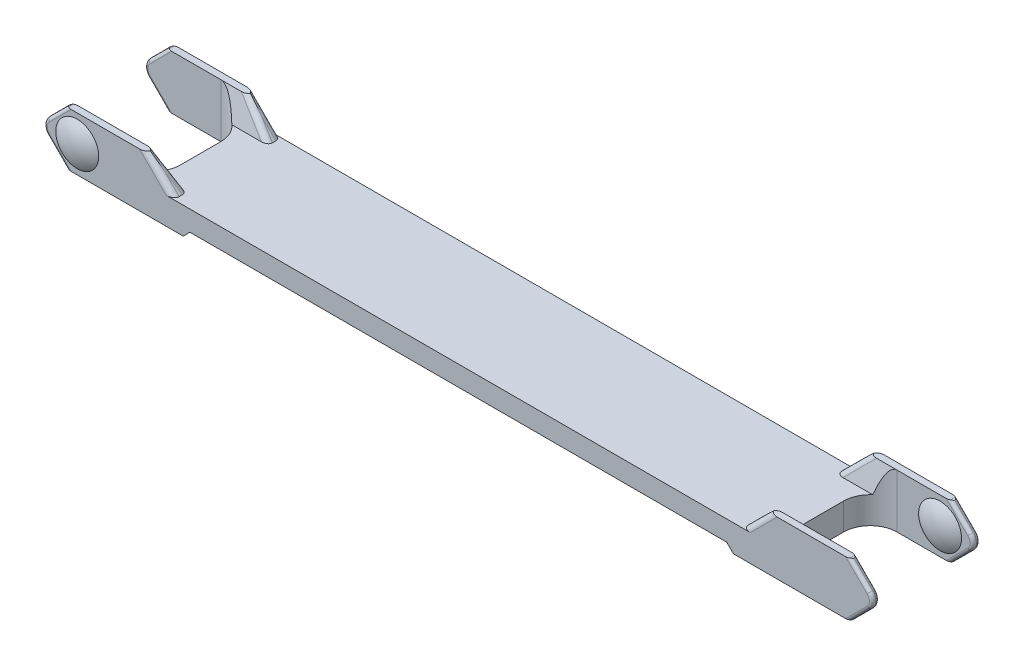
SolidWorks part; units mm, degrees
ref_plane "Front Plane" through (0, 0, 0) normal (0, 0, 1) x (1, 0, 0)
ref_plane "Top Plane" through (0, 0, 0) normal (0, 1, 0) x (1, 0, 0)
ref_plane "Right Plane" through (0, 0, 0) normal (1, 0, 0) x (0, 0, -1)
sketch "Sketch1" plane through (0, 0, 0) normal (0, 1, 0) x (1, 0, 0)
  line L0 (-73.66, 12.7) -> (-73.66, -12.7) construction
  line L1 (-99.06, -12.7) -> (99.06, -12.7)
  line L2 (-99.06, -12.7) -> (-99.06, -11.1125)
  line L3 (-99.06, 12.7) -> (99.06, 12.7)
  line L5 (-99.06, -12.7) -> (99.06, 12.7) construction
  line L6 (-99.06, 12.7) -> (99.06, -12.7) construction
  line L7 (-99.06, 11.1125) -> (-80.01, 11.1125)
  line L8 (-73.66, 4.7625) -> (-73.66, -4.7625)
  line L9 (-80.01, -11.1125) -> (-99.06, -11.1125)
  line L10 (-99.06, 11.1125) -> (-99.06, 12.7)
  line L11 (0, 0) -> (0, 12.7) construction
  line L12 (99.06, 12.7) -> (99.06, 11.1125)
  line L13 (99.06, -12.7) -> (99.06, -11.1125)
  line L14 (80.01, -11.1125) -> (99.06, -11.1125)
  line L15 (73.66, 4.7625) -> (73.66, -4.7625)
  line L16 (99.06, 11.1125) -> (80.01, 11.1125)
  arc A0 (-73.66, -4.7625) -> (-80.01, -11.1125) centre (-80.01, -4.7625) cw
  arc A1 (-80.01, 11.1125) -> (-73.66, 4.7625) centre (-80.01, 4.7625) cw
  arc A2 (73.66, -4.7625) -> (80.01, -11.1125) centre (80.01, -4.7625) ccw
  arc A3 (80.01, 11.1125) -> (73.66, 4.7625) centre (80.01, 4.7625) ccw
  point P0 (0, 0)
  point P14 (-73.66, -11.1125)
  point P17 (-73.66, 11.1125)
  dimension "D6" = 6.35
  dimension "D1" = 198.12
  dimension "D2" = 25.4
  dimension "D3" = 25.4
  dimension "D4" = 1.5875
  dimension "D5" = 1.5875
extrude "Boss-Extrude1" add sketch "Sketch1" along normal blind 12.7
sketch "Sketch3" plane through (-99.06, 0, 0) normal (-1, 0, 0) x (0, 0, 1)
  line L7 (11.1125, 12.7) -> (4.7625, 12.7) construction
  line L8 (-4.7625, 12.7) -> (4.7625, 12.7) construction
  line L9 (-4.7625, 12.7) -> (-11.1125, 12.7) construction
  line L19 (11.1125, 12.7) -> (4.7625, 12.7)
  line L20 (-4.7625, 12.7) -> (4.7625, 12.7)
  line L21 (-4.7625, 12.7) -> (-11.1125, 12.7)
  line L24 (0, 0) -> (0, 12.7) construction
  line L25 (-12.7, 6.35) -> (12.7, 6.35) construction
  line L26 (-9.525, 6.35) -> (9.525, 6.35)
  line L27 (-11.1125, 12.7) -> (-9.525, 6.35)
  line L28 (9.525, 6.35) -> (11.1125, 12.7)
  point P17 (0, 6.35)
  dimension "D1" = 19.05
  dimension "D2" = 6.35
extrude "Cut-Extrude2" cut sketch "Sketch3" against normal through all
sketch "Sketch2" plane through (0, 0, 12.7) normal (0, 0, 1) x (1, 0, 0)
  line L0 (-97.2639, 8.1461) -> (-92.71, 12.7)
  line L1 (-97.2639, 4.5539) -> (-92.71, 0)
  line L2 (-73.66, 12.7) -> (-73.66, 0) construction
  line L3 (0, 0) -> (0, 12.7) construction
  line L4 (-99.06, 0) -> (99.06, 0)
  line L5 (99.06, 0) -> (99.06, 12.7)
  line L6 (99.06, 12.7) -> (-99.06, 12.7)
  line L7 (-99.06, 12.7) -> (-99.06, 0)
  line L8 (-99.06, 0) -> (-92.71, 0)
  line L9 (99.06, 0) -> (99.06, 12.7)
  line L10 (99.06, 12.7) -> (92.71, 12.7)
  line L11 (-99.06, 12.7) -> (-99.06, 0)
  line L12 (73.66, 12.7) -> (73.66, 0) construction
  line L13 (97.2639, 4.5539) -> (92.71, 0)
  line L14 (97.2639, 8.1461) -> (92.71, 12.7)
  line L15 (99.06, 12.7) -> (99.06, 0)
  line L16 (-99.06, 0) -> (-99.06, 12.7)
  line L17 (-99.06, 6.35) -> (99.06, 6.35) construction
  line L18 (-73.66, 12.7) -> (-67.31, 6.35)
  line L19 (-67.31, 6.35) -> (67.31, 6.35)
  line L20 (67.31, 6.35) -> (73.66, 12.7)
  line L21 (-92.71, 12.7) -> (-99.06, 12.7)
  line L22 (92.71, 0) -> (99.06, 0)
  line L23 (73.66, 12.7) -> (-73.66, 12.7)
  arc A0 (97.2639, 4.5539) -> (97.2639, 8.1461) centre (95.4679, 6.35) ccw
  arc A1 (-97.2639, 8.1461) -> (-97.2639, 4.5539) centre (-95.4679, 6.35) ccw
  line M12 (-99.06, 0) -> (99.06, 0)
  line M13 (99.06, 0) -> (99.06, 12.7)
  line M14 (99.06, 12.7) -> (-99.06, 12.7)
  line M15 (-99.06, 12.7) -> (-99.06, 0)
  dimension "D7" = 2.54
  dimension "D2" = 45
  dimension "D3" = 45
  dimension "D4" = 25.4
  dimension "D5" = 45
  dimension "D6" = 45
  dimension "D1" = 0
extrude "Cut-Extrude1" cut sketch "Sketch2" against normal through all contours L19 L20 L18 M14 | A0 L13 L14 M12 M13 M14 | A1 L0 L1 M14 M15 M12 region at (-98.1499, 6.35, 12.7) region at (0, 9.5727, 12.7) region at (95.0874, 2.1766, 12.7)
ref_plane "Plane1" through (-90.17, 0, 0) normal (-1, 0, 0) x (0, 0, 1)
sketch "Sketch4" plane through (-90.17, 0, 0) normal (-1, 0, 0) x (0, 0, 1)
  line L0 (0, 6.35) -> (17.6113, 6.35) construction
  line L1 (4.7625, 6.35) -> (-4.7625, 6.35) construction
  line L2 (12.7, 6.35) -> (12.7, 11.43)
  line L3 (12.7, 8.1461) -> (12.7, 12.7) construction
  line L4 (12.7, 6.35) -> (14.2875, 6.35)
  arc A0 (12.7, 11.43) -> (14.2875, 6.35) centre (5.3658, 6.35) cw
  dimension "D3" = 8.9217
  dimension "D1" = 5.08
  dimension "D2" = 1.5875
revolve "Revolve1" add sketch "Sketch4" angle 360 about L0
ref_plane "Plane2" through (0, 0, 0) normal (0, 0, 1) x (1, 0, 0)
mirror "Mirror1" about plane through (0, 0, 0) normal (0, 0, 1) of "Revolve1"
ref_plane "Plane3" through (90.17, 0, 0) normal (1, 0, 0) x (0, 0, -1)
sketch "Sketch5" plane through (90.17, 0, 0) normal (1, 0, 0) x (0, 0, -1)
  line L0 (0, 6.35) -> (15.4068, 6.35) construction
  line L1 (4.7625, 6.35) -> (-4.7625, 6.35) construction
  line L2 (11.1125, 6.35) -> (11.1125, 11.43)
  line L3 (11.1125, 12.7) -> (11.1125, 0) construction
  line L4 (11.1125, 12.7) -> (11.1125, 8.1461) construction
  line L5 (11.1125, 6.35) -> (9.525, 6.35)
  arc A0 (11.1125, 11.43) -> (9.525, 6.35) centre (18.4467, 6.35) ccw
  dimension "D3" = 8.9217
  dimension "D1" = 5.08
  dimension "D2" = 1.5875
revolve "Revolve2" add sketch "Sketch5" angle 360 about L0
mirror "Mirror2" about plane through (0, 0, 0) normal (0, 0, 1) of "Revolve2"
ref_plane "Plane4" through (0, 0, 0) normal (1, 0, 0) x (0, 0, -1)
sketch "Sketch6" plane through (0, 0, 0) normal (1, 0, 0) x (0, 0, -1)
  line L5 (-12.7, 0) -> (-11.1125, 0)
  line L6 (-11.1125, 0) -> (-12.7, 0) construction
  line L7 (-11.1125, 0) -> (-12.7, 1.5875)
  line L8 (-12.7, 11.43) -> (-12.7, 1.27) construction
  line L9 (-12.7, 1.5875) -> (-12.7, 0)
  line L10 (0, 0) -> (0, 6.35) construction
  line L11 (-4.7625, 6.35) -> (4.7625, 6.35) construction
  line L12 (11.1125, 0) -> (12.7, 1.5875)
  line L13 (12.7, 0) -> (11.1125, 0)
  line L14 (12.7, 1.5875) -> (12.7, 0)
  dimension "D1" = 1.5875
  dimension "D2" = 1.5875
extrude "Cut-Extrude3" cut sketch "Sketch6" against normal mid plane 127
chamfer "Chamfer1" distance 1.5875 angle 45 4 edges at (63.5, 0, 11.9062) (63.5, 0, -11.9062) (-63.5, 0, -11.9062) (-63.5, 0, 11.9062)
fillet "Fillet1" radius 0.762 28 edges at (94.987, 2.277, -12.7) (98.0079, 6.35, -12.7) (94.987, 2.277, -11.1125) (98.0079, 6.35, -11.1125) (94.987, 2.277, 12.7) (98.0079, 6.35, 12.7) (94.987, 2.277, 11.1125) (98.0079, 6.35, 11.1125) (-94.987, 2.277, -11.1125) (-98.0079, 6.35, -11.1125) (-94.987, 2.277, -12.7) (-98.0079, 6.35, -12.7) (-94.987, 2.277, 11.1125) (-98.0079, 6.35, 11.1125) (-94.987, 2.277, 12.7) (-98.0079, 6.35, 12.7) (92.71, 12.7, -11.9062) (94.987, 10.423, -12.7) (94.987, 10.423, -11.1125) (94.987, 10.423, 12.7) (92.71, 12.7, 11.9063) (94.987, 10.423, 11.1125) (-94.987, 10.423, -11.1125) (-94.987, 10.423, -12.7) (-92.71, 12.7, -11.9062) (-94.987, 10.423, 11.1125) (-92.71, 12.7, 11.9063) (-94.987, 10.423, 12.7)
fillet "Fillet2" radius 1.27 8 edges at (-70.485, 9.525, -12.7) (-70.485, 9.525, -10.3188) (-70.485, 9.525, 10.3187) (-70.485, 9.525, 12.7) (70.485, 9.525, -12.7) (70.485, 9.525, -10.3188) (70.485, 9.525, 12.7) (70.485, 9.525, 10.3187)
